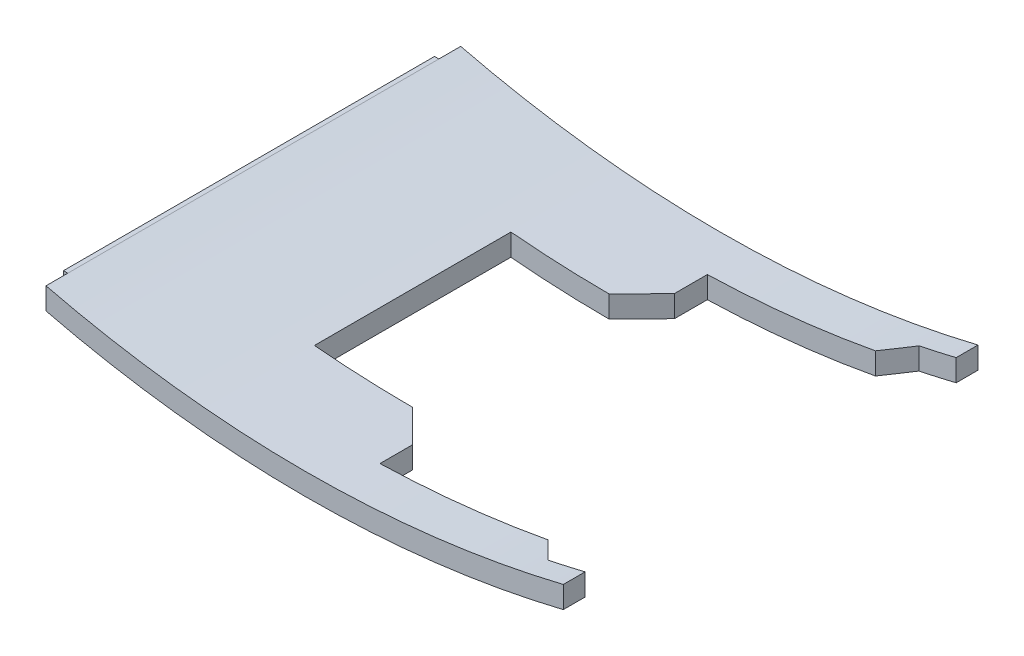
SolidWorks part; units mm, degrees
ref_plane "Front Plane" through (0, 0, 0) normal (0, 0, 1) x (1, 0, 0)
ref_plane "Top Plane" through (0, 0, 0) normal (0, 1, 0) x (1, 0, 0)
ref_plane "Right Plane" through (0, 0, 0) normal (1, 0, 0) x (0, 0, -1)
sketch "Sketch1" plane through (0, 0, 0) normal (0, 0, 1) x (1, 0, 0)
  line L0 (0, 0) -> (0, 2.54)
  line L1 (60.198, 0) -> (60.198, 2.54)
  arc A0 (0, 0) -> (60.198, 0) centre (30.099, 123.3817) ccw
  arc A1 (0, 2.54) -> (60.198, 2.54) centre (30.099, 125.9217) ccw
  dimension "D1" = 127
  dimension "D2" = 60.198
  dimension "D3" = 2.54
extrude "Boss-Extrude1" add sketch "Sketch1" along normal blind 48.26
ref_plane "Plane1" through (0, 3.81, 0) normal (0, 1, 0) x (1, 0, 0)
sketch "Sketch4" plane through (0, 3.81, 0) normal (0, 1, 0) x (1, 0, 0)
  line L0 (60.198, -48.26) -> (60.198, 0) construction
  line L1 (60.198, -35.56) -> (18.542, -35.56)
  line L2 (60.198, -35.56) -> (60.198, -12.7)
  line L3 (60.198, -12.7) -> (18.542, -12.7)
  line L4 (18.542, -35.56) -> (18.542, -12.7)
  line L5 (0, -24.13) -> (18.542, -24.13) construction
  line L6 (0, -48.26) -> (0, 0) construction
  dimension "D1" = 22.86
  dimension "D2" = 18.542
extrude "Cut-Extrude1" cut sketch "Sketch4" against normal blind 25.4
sketch "Sketch5" plane through (0, 3.81, 0) normal (0, 1, 0) x (1, 0, 0)
  line L0 (33.782, -12.7) -> (33.782, -5.08)
  line L1 (60.198, -12.7) -> (18.542, -12.7) construction
  line L2 (33.782, -5.08) -> (56.388, -5.08)
  line L3 (60.198, -12.7) -> (60.198, 0) construction
  line L4 (33.782, -12.7) -> (60.198, -12.7)
  line L5 (60.198, -12.7) -> (60.198, -3.81)
  line L6 (18.542, -35.56) -> (18.542, -12.7) construction
  line L7 (60.198, 0) -> (0, 0) construction
  line L8 (18.542, -24.13) -> (0, -24.13) construction
  line L9 (33.782, -35.56) -> (60.198, -35.56)
  line L10 (33.782, -35.56) -> (33.782, -43.18)
  line L11 (33.782, -43.18) -> (56.388, -43.18)
  line L13 (60.198, -48.26) -> (60.198, -35.56) construction
  line L15 (56.388, -5.08) -> (56.388, -2.54)
  line L16 (56.388, -2.54) -> (60.198, -2.54)
  line L17 (60.198, -3.81) -> (60.198, -2.54)
  line L18 (60.198, -35.56) -> (60.198, -45.72)
  line L21 (56.388, -43.18) -> (56.388, -45.72)
  line L22 (56.388, -45.72) -> (60.198, -45.72)
  line L26 (0, -48.26) -> (60.198, -48.26) construction
  point P21 (57.023, -5.08)
  point P26 (57.023, -43.18)
  dimension "D1" = 15.24
  dimension "D2" = 5.08
  dimension "D3" = 2.54
  dimension "D4" = 3.81
  dimension "D5" = 2.54
extrude "Cut-Extrude2" cut sketch "Sketch5" against normal blind 25.4
sketch "Sketch6" plane through (0, 0, 0) normal (-1, 0, 0) x (0, 0, 1)
  line L0 (48.26, 2.54) -> (0, 2.54) construction
  line L1 (2.54, 2.54) -> (45.72, 2.54)
  line L2 (2.54, 2.54) -> (2.54, 0)
  line L3 (2.54, 0) -> (45.72, 0)
  line L4 (45.72, 2.54) -> (45.72, 0)
  line L5 (48.26, 0) -> (0, 0) construction
  line L6 (0, 2.54) -> (0, 0) construction
  line L7 (48.26, 2.54) -> (48.26, 0) construction
  dimension "D1" = 2.54
  dimension "D2" = 2.54
extrude "Boss-Extrude2" add sketch "Sketch6" along normal blind 0.508
chamfer "Chamfer2" distance 3.048 angle 45 2 edges at (56.388, 0.4024, 43.18) (56.388, 0.4024, 5.08)
chamfer "Chamfer3" distance 3.81 angle 45 2 edges at (33.782, -2.2949, 12.7) (33.782, -2.2949, 35.56)
